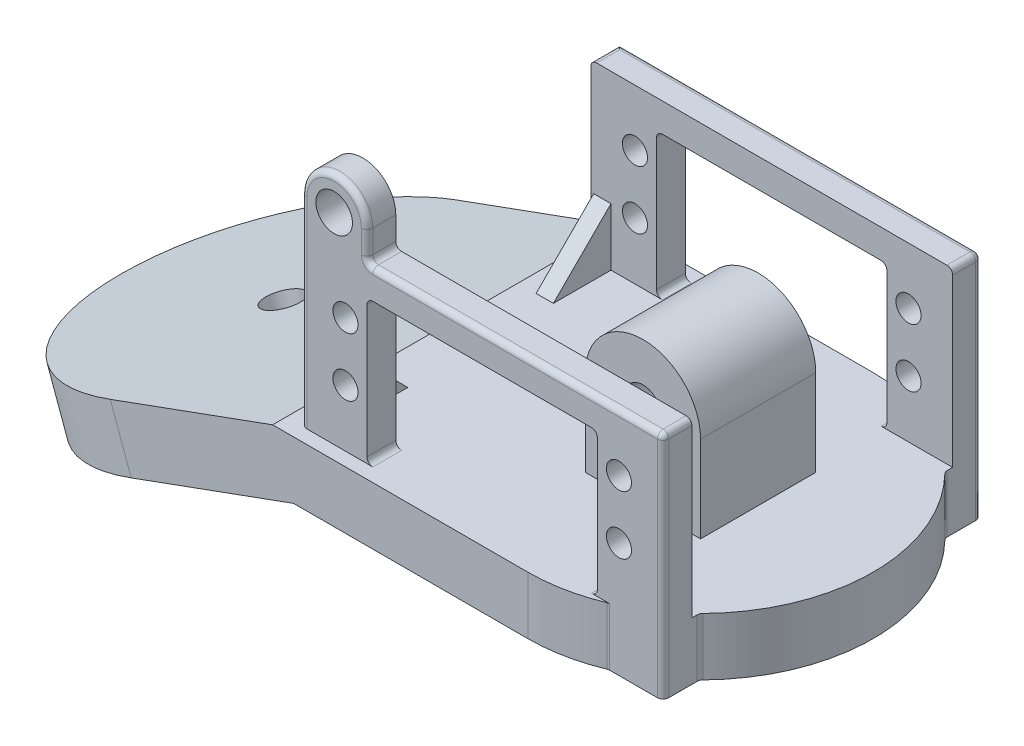
SolidWorks part; units mm, degrees
ref_plane "Plan de face" through (0, 0, 0) normal (0, 0, 1) x (1, 0, 0)
ref_plane "Plan de dessus" through (0, 0, 0) normal (0, 1, 0) x (1, 0, 0)
ref_plane "Plan de droite" through (0, 0, 0) normal (1, 0, 0) x (0, 0, -1)
sketch "Esquisse5" plane through (0, 0, 0) normal (0, 1, 0) x (1, 0, 0)
  line L0 (42.5, 0) -> (-42.5, 0) construction
  line L1 (42.5, -30) -> (-42.5, -30)
  line L2 (42.5, 30) -> (-42.5, 30)
  arc A0 (42.5, -30) -> (42.5, 30) centre (42.5, 0) ccw
  arc A1 (-42.5, 30) -> (-42.5, -30) centre (-42.5, 0) ccw
  point P2 (0, 0)
  dimension "D2" = 30
  dimension "D1" = 85
extrude "Boss.-Extru.3" add sketch "Esquisse5" along normal mid plane 10
sketch "Esquisse36" plane through (0, 0, 0) normal (0, 0, 1) x (1, 0, 0)
  line L0 (0, 0) -> (9.0993, -25)
  line L1 (9.0993, -25) -> (-112.5, -25)
  line L2 (-112.5, -25) -> (-112.5, 35)
  line L3 (-112.5, 35) -> (-12.739, 35)
  line L4 (-12.739, 35) -> (0, 0)
  line L5 (42.5, -5) -> (-42.5, -5) construction
  line L6 (42.5, 5) -> (-42.5, 5) construction
  line L7 (-42.5, 5) -> (-42.5, -5) construction
  dimension "D1" = 180
  dimension "D2" = 20
  dimension "D3" = 70
  dimension "D4" = 30
  dimension "D5" = 70
sketch "Esquisse7" plane through (0, 0, 0) normal (0, 0, 1) x (1, 0, 0)
  line L0 (42.5, 5) -> (32.5, 5)
  line L1 (-42.5, 5) -> (42.5, 5) construction
  line L2 (32.5, 5) -> (32.5, 20)
  line L3 (32.5, 20) -> (52.5, 20)
  line L4 (52.5, 20) -> (52.5, 5)
  line L5 (72.5, 5) -> (42.5, 5) construction
  line L6 (52.5, 5) -> (42.5, 5)
  arc A0 (32.5, 20) -> (52.5, 20) centre (42.5, 20) cw
  circle A1 centre (42.5, 20) radius 3.175
  dimension "D1" = 10
  dimension "D3" = 6.35
  dimension "D2" = 15
extrude "Boss.-Extru.5" add sketch "Esquisse7" along normal mid plane 20 contours A1 L3 A0 | A1 L3 L2 L0 L6 L4 region at (42.5, 12.1572, 0) region at (42.5, 24.5689, 0)
sketch "Esquisse10" plane through (0, -5, 0) normal (0, -1, 0) x (1, 0, 0)
  point P0 (42.5, 0)
ref_plane "Plan1" through (0, 0, 22.64) normal (0, 0, 1) x (1, 0, 0)
sketch "Esquisse13" plane through (0, 0, 22.64) normal (0, 0, 1) x (1, 0, 0)
  line L0 (-42.5, 5) -> (42.5, 5) construction
  line L1 (5.8, 5) -> (58.63, 5)
  line L2 (5.8, 5) -> (5.8, 29.91) construction
  line L3 (5.8, 29.91) -> (58.63, 29.91) construction
  line L4 (58.63, 5) -> (58.63, 29.91) construction
  line L5 (5.8, 5) -> (0.8, 5)
  line L6 (0.8, 5) -> (0.8, 34.91)
  line L7 (0.8, 34.91) -> (63.63, 34.91)
  line L8 (63.63, 34.91) -> (63.63, 5)
  line L9 (63.63, 5) -> (58.63, 5)
  line L10 (63.63, 5) -> (58.63, 5)
  line L11 (0.8, 5) -> (5.8, 5)
  line L12 (12.215, 5) -> (12.215, 29.91)
  line L13 (12.215, 29.91) -> (52.215, 29.91)
  line L14 (52.215, 29.91) -> (52.215, 5)
  line L15 (52.215, 5) -> (12.215, 5)
  circle A0 centre (42.5, 20) radius 3.175 construction
  circle A2 centre (55.97, 25.08) radius 2.18
  circle A3 centre (55.97, 14.92) radius 2.18
  circle A4 centre (8.47, 25.08) radius 2.18
  circle A5 centre (8.47, 14.92) radius 2.18
  point P6 (58.63, 17.455)
  point P24 (32.215, 29.91)
  point P26 (32.215, 34.91)
  dimension "D4" = 5
  dimension "D7" = 4.36
  dimension "D8" = 47.5
  dimension "D12" = 10.16
  dimension "D1" = 52.83
  dimension "D2" = 16.13
  dimension "D3" = 24.91
  dimension "D5" = 4.83
  dimension "D6" = 2.67
  dimension "D9" = 47.5
  dimension "D10" = 0
  dimension "D11" = 0
  dimension "D13" = 0
  dimension "D14" = 5
  dimension "D15" = 5
  dimension "D16" = 40
  dimension "D17" = 0
  dimension "D18" = 0
extrude "Boss.-Extru.8" add sketch "Esquisse13" along normal blind 5 contours L13 L14 L1 L9 L8 L7 L6 L5 L12 A5 A4 A3 A2 region at (3.3, 5.6959, 22.64)
ref_plane "Plan12" through (2.8, 0, 0) normal (-1, 0, 0) x (0, 0, 1)
mirror "Symétrie2" about plane through (0, 0, 0) normal (0, 0, 1) of "Boss.-Extru.8"
sketch "Esquisse14" plane through (0, 0, 0) normal (0, 0, 1) x (1, 0, 0)
  point P0 (42.5, 20)
sketch "Esquisse33" plane through (0, 5, 0) normal (0, -1, 0) x (1, 0, 0)
  line L0 (54.1632, -27.64) -> (63.63, -27.64) construction
  line L1 (63.63, 27.64) -> (54.1632, 27.64)
  line L2 (63.63, 27.64) -> (63.63, -27.64)
  line L3 (63.63, -27.64) -> (54.1632, -27.64)
  line L4 (54.1632, 27.64) -> (54.1632, -27.64)
  dimension "D1" = 0
  dimension "D2" = 0
extrude "Boss.-Extru.10" add sketch "Esquisse33" along normal up to surface (10 mm away) up to face at (0, -5, 0)
sketch "Esquisse34" plane through (0, 0, 0) normal (0, 1, 0) x (1, 0, 0)
  line L0 (0, 0) -> (0, 29.4868) construction
extrude "Enlèv. mat.-Extru.6" cut sketch "Esquisse36" against normal mid plane 130
ref_plane "Plan11" through (0, 0, 0) normal (-0.342, 0.9397, 0) x (0, 0, -1)
sketch "Esquisse35" plane through (0, 0, 0) normal (-0.342, 0.9397, 0) x (0, 0, -1)
  circle A0 centre (0, 30) radius 30
  dimension "D1" = 60
  dimension "D2" = 0
extrude "Boss.-Extru.11" add sketch "Esquisse35" along normal mid plane 10.64
sketch "Esquisse37" plane through (0, 0, 0) normal (0, 0, 1) x (1, 0, 0)
sketch "Esquisse38" plane through (-1.8195, 4.9992, 0) normal (-0.342, 0.9397, 0) x (0.9397, 0.342, 0)
  point P1 (-30, 0)
sketch "Esquisse39" plane through (1.8195, -4.9992, 0) normal (0.342, -0.9397, 0) x (0.9397, 0.342, 0)
  point P0 (-30, 0)
sketch "Esquisse40" plane through (0, 0, 0) normal (0, 0, 1) x (1, 0, 0)
  line L0 (-26.3712, -15.2598) -> (-30.0103, -5.2614)
  line L1 (-26.3712, -15.2598) -> (1.8195, -4.9992)
  line L2 (-30.0103, -5.2614) -> (-1.8195, 4.9992)
  line L3 (1.8195, -4.9992) -> (-1.8195, 4.9992)
  dimension "D1" = 0
extrude "Boss.-Extru.12" add sketch "Esquisse40" along normal mid plane 60
sketch "Esquisse41" plane through (-1.8195, 4.9992, 0) normal (-0.342, 0.9397, 0) x (0.9397, 0.342, 0)
  circle A0 centre (-30, 0) radius 3.175
  dimension "D1" = 6.35
extrude "Enlèv. mat.-Extru.7" cut sketch "Esquisse41" against normal blind 60
sketch "Esquisse42" plane through (0, 0, 27.64) normal (0, 0, 1) x (1, 0, 0)
  line L0 (0.8, 34.91) -> (0.8, 39.91)
  line L1 (0.8, 39.91) -> (12.215, 39.91)
  line L2 (12.215, 39.91) -> (12.215, 34.91)
  line L3 (0.8, 34.91) -> (63.63, 34.91) construction
  line L4 (12.215, 34.91) -> (0.8, 34.91)
  line L5 (12.215, 5) -> (12.215, 29.91) construction
  arc A0 (0.8, 39.91) -> (12.215, 39.91) centre (6.5075, 39.91) cw
  circle A1 centre (6.5075, 39.91) radius 3.175
  line M15 (63.63, 34.91) -> (0.8, 34.91)
  dimension "D3" = 6.35
  dimension "D1" = 5
  dimension "D2" = 0
extrude "Boss.-Extru.13" add sketch "Esquisse42" against normal up to surface (5 mm away) contours A1 L1 A0 | A1 L1 L0 L2 M15 region at (0.9246, 37.41, 27.64) region at (6.5075, 45.4899, 27.64) up to face at (10.65, 14.92, 22.64)
sketch "Esquisse45" plane through (2.8, 0, 0) normal (-1, 0, 0) x (0, 0, 1)
  line L0 (22.64, 14.9996) -> (12.64, 4.9996)
  line L1 (22.64, 5) -> (22.64, 39.91) construction
  line L2 (30, 4.9996) -> (-30, 4.9996) construction
  dimension "D1" = 10
  dimension "D2" = 10
rib "Nervure4" sketch "Esquisse45" sketch "Esquisse45" thickness 3 extrusion direction parallel to sketch draft on no parameters "D1"=3
fillet "Congé1" radius 1 6 edges at (54.1632, 0, 27.64) (63.63, 14.955, 27.64) (63.63, 0, 21.2961) (54.1632, 0, -27.64) (63.63, 0, -21.2961) (63.63, 14.955, -27.64)
mirror "Symétrie3" about plane through (0, 0, 0) normal (0, 0, 1) of "Nervure4"
fillet "Congé2" radius 1 19 edges at (0.8, 22.455, 27.64) (6.5075, 45.6175, 27.64) (12.215, 37.41, 27.64) (31.715, 34.91, -27.64) (63.3371, 34.91, -27.3471) (37.4225, 34.91, 27.64) (63.3371, 34.91, 27.3471) (63.63, 34.91, -24.64) (0.8, 34.91, -25.14) (52.215, 5, -25.14) (52.215, 29.91, -25.14) (12.215, 29.91, -25.14) (12.215, 5, -25.14) (12.215, 5, 25.14) (52.215, 5, 25.14) (52.215, 29.91, 25.14) (12.215, 29.91, 25.14) (12.215, 34.91, 25.14) (63.63, 34.91, 24.64)
